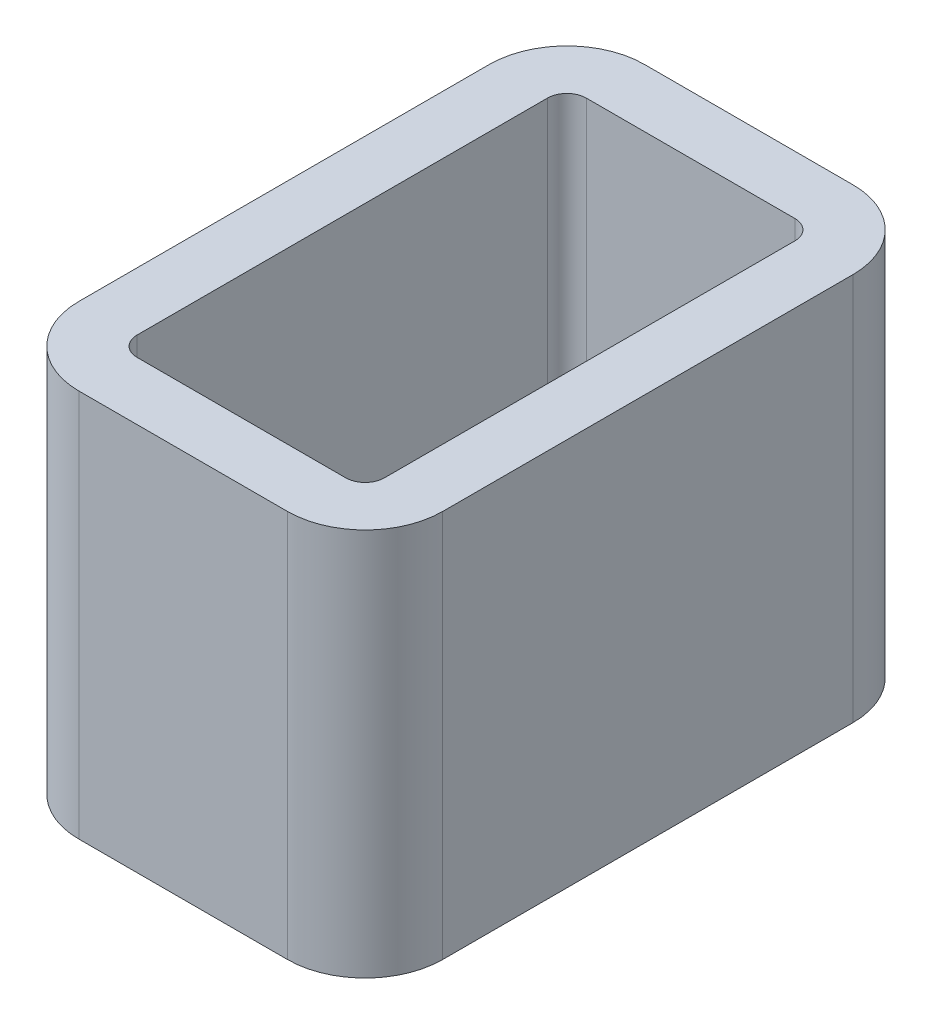
SolidWorks part; units mm, degrees
ref_plane "Front Plane" through (0, 0, 0) normal (0, 0, 1) x (1, 0, 0)
ref_plane "Top Plane" through (0, 0, 0) normal (0, 1, 0) x (1, 0, 0)
ref_plane "Right Plane" through (0, 0, 0) normal (1, 0, 0) x (0, 0, -1)
sketch "Sketch1" plane through (0, 0, 0) normal (0, 1, 0) x (1, 0, 0)
  line L0 (-5.375, 14.575) -> (5.375, 14.575)
  line L1 (-5.375, 11.575) -> (5.375, 11.575)
  line L2 (-6.375, 10.575) -> (-6.375, -10.575)
  line L3 (-5.375, -11.575) -> (5.375, -11.575)
  line L4 (6.375, 10.575) -> (6.375, -10.575)
  line L5 (-6.375, 11.575) -> (6.375, -11.575) construction
  line L6 (-6.375, -11.575) -> (6.375, 11.575) construction
  line L7 (9.375, 10.575) -> (9.375, -10.575)
  line L8 (-5.375, -14.575) -> (5.375, -14.575)
  line L9 (-9.375, 10.575) -> (-9.375, -10.575)
  arc A0 (-6.375, -10.575) -> (-5.375, -11.575) centre (-5.375, -10.575) ccw
  arc A1 (5.375, -11.575) -> (6.375, -10.575) centre (5.375, -10.575) ccw
  arc A2 (5.375, 11.575) -> (6.375, 10.575) centre (5.375, 10.575) cw
  arc A3 (-5.375, 11.575) -> (-6.375, 10.575) centre (-5.375, 10.575) ccw
  arc A4 (5.375, 14.575) -> (9.375, 10.575) centre (5.375, 10.575) cw
  arc A5 (5.375, -14.575) -> (9.375, -10.575) centre (5.375, -10.575) ccw
  arc A6 (-9.375, -10.575) -> (-5.375, -14.575) centre (-5.375, -10.575) ccw
  arc A7 (-5.375, 14.575) -> (-9.375, 10.575) centre (-5.375, 10.575) ccw
  point P0 (0, 0)
  dimension "D3" = 1
  dimension "D1" = 12.75
  dimension "D2" = 23.15
  dimension "D4" = 3
extrude "Boss-Extrude1" add sketch "Sketch1" along normal blind 20
